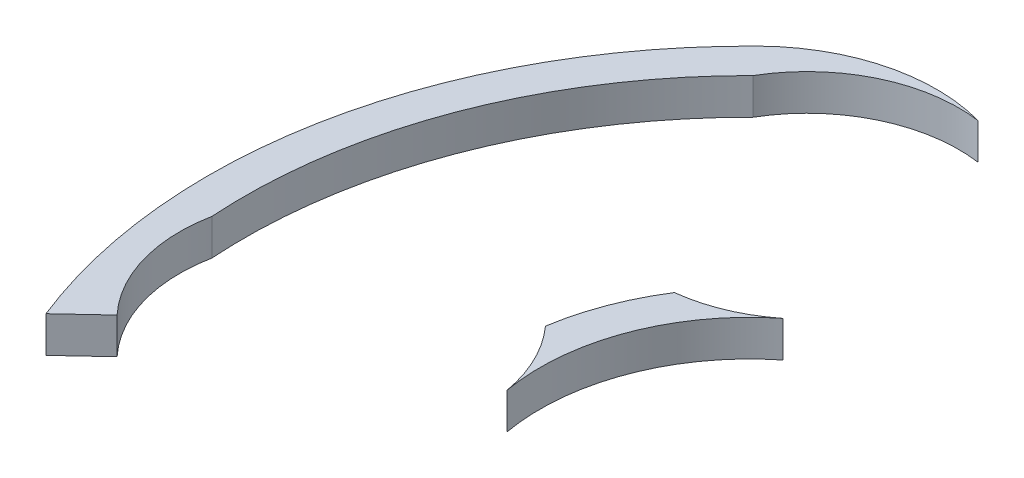
SolidWorks part; units mm, degrees
ref_plane "Plan de face" through (0, 0, 0) normal (0, 0, 1) x (1, 0, 0)
ref_plane "Plan de dessus" through (0, 0, 0) normal (0, 1, 0) x (1, 0, 0)
ref_plane "Plan de droite" through (0, 0, 0) normal (1, 0, 0) x (0, 0, -1)
sketch "Esquisse1" plane through (0, 0, 0) normal (0, 1, 0) x (1, 0, 0)
  line L0 (-85.9864, -39.221) -> (-80.901, -34.4645)
  line L3 (-9.4508, 5.6286) -> (-14.9085, -3.5351) construction
  line L5 (3.3105, -15.9387) -> (9.4508, -5.6286) construction
  line L12 (0, 0) -> (-80, 0) construction
  line L13 (-64.4502, -24.994) -> (-51.2217, 24.3754) construction
  line L14 (-65, 0) -> (-64.4502, -24.994) construction
  arc A0 (-44.8834, -16.4709) -> (3.3105, -15.9387) centre (-21.2415, 25) ccw construction
  arc A1 (-19.5917, -4.1368) -> (-14.9085, -3.5351) centre (-17.486, -2) ccw construction
  arc A2 (-19.5917, -4.1368) -> (-34.3894, 11.2538) centre (258.274, 277.8334) cw construction
  arc A3 (-13.5326, 17.4331) -> (-23.8264, -39.4451) centre (-16.3245, -11.4322) ccw
  arc A4 (-45.0056, 6.8269) -> (-49.9076, -6.124) centre (-16.3245, -11.4322) ccw
  arc A5 (-13.0513, 22.4098) -> (-25.1198, -44.2749) centre (-16.3245, -11.4322) ccw construction
  arc A6 (-65.5922, 38.294) -> (-86.1705, -16.0732) centre (-16.3245, -11.4322) ccw
  arc A36 (-51.2217, 24.3754) -> (-64.4502, -24.994) centre (-16.3245, -11.4322) ccw construction
  arc A37 (-68.6703, 42.2792) -> (-85.9864, -39.221) centre (-16.3245, -11.4322) ccw
  arc A41 (9.4508, -5.6286) -> (-9.4508, 5.6286) centre (0, 0) ccw construction
  arc A42 (-16.402, 38.5677) -> (-47.4539, -50.5598) centre (-16.3245, -11.4322) ccw construction
  arc A43 (-44.6149, 48.4866) -> (-34.3894, 11.2538) centre (-47.4709, 27.6817) ccw
  arc A44 (-44.6149, 48.4866) -> (-68.6703, 42.2792) centre (-51.2217, 24.3754) ccw
  arc A45 (-44.8834, -16.4709) -> (-80.901, -34.4645) centre (-65.564, -20.1196) ccw
  point P78 (-56.6847, 2.6915)
  point P85 (-65, 0)
  dimension "D4" = 25
  dimension "D5" = 12
  dimension "D6" = 21
  dimension "D7" = 5
  dimension "D8" = 25
  dimension "D9" = 5
  dimension "D10" = 3
  dimension "D11" = 17.6
  dimension "D18" = 80
  dimension "D20" = 75
  dimension "D26" = 11
  dimension "D13" = 50
  dimension "D14" = 21
  dimension "D12" = 2
  dimension "D22" = 25
  dimension "D23" = 75
  dimension "D24" = 28
  dimension "D25" = 15
  dimension "D30" = 5
  dimension "D32" = 5
extrude "Boss.-Extru.1" add sketch "Esquisse1" along normal blind 5 contours A45 A3 A43 A44 A37 L0 | A45 A3 A43 A4 region at (-88.7072, 0, -3.9467) region at (-45.0114, 0, 0.5741)
